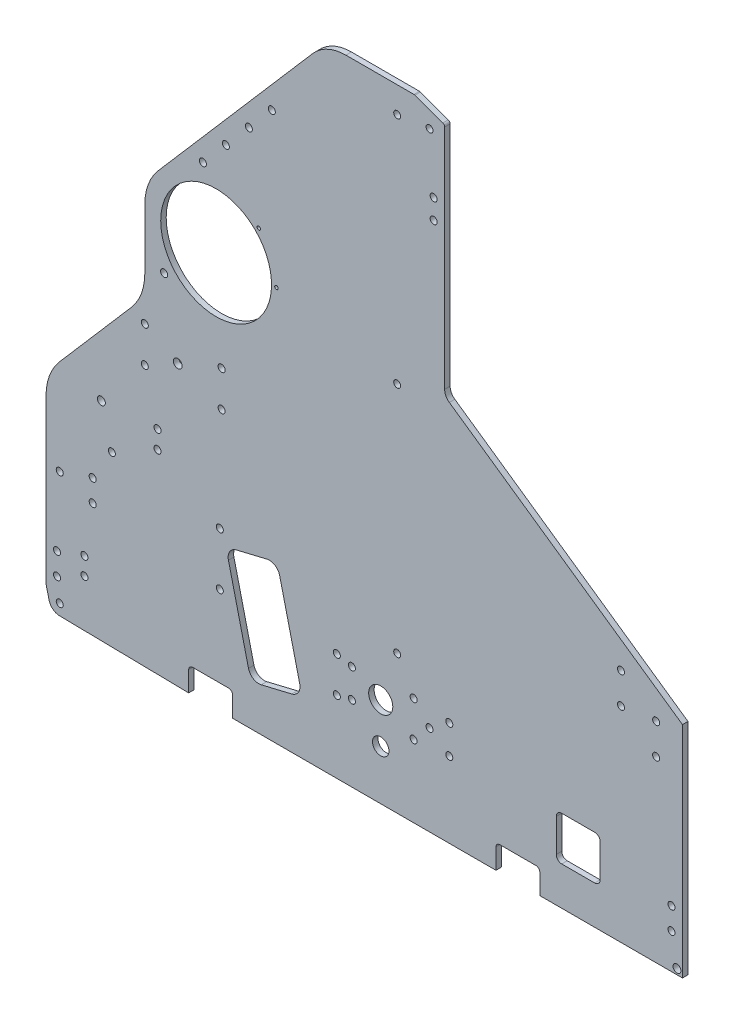
SolidWorks part; units mm, degrees
ref_plane "Front Plane" through (0, 0, 0) normal (0, 0, 1) x (1, 0, 0)
ref_plane "Top Plane" through (0, 0, 0) normal (0, 1, 0) x (1, 0, 0)
ref_plane "Right Plane" through (0, 0, 0) normal (1, 0, 0) x (0, 0, -1)
sketch "Sketch1" plane through (0, 0, 0) normal (0, 0, 1) x (1, 0, 0)
  line L0 (82.55, -20.32) -> (82.55, -6.35)
  line L2 (0, 0) -> (0, 157.48)
  line L4 (368.3, -20.32) -> (368.3, 106.68)
  line L5 (82.55, -6.35) -> (107.95, -6.35)
  line L6 (107.95, -6.35) -> (107.95, -20.32)
  line L7 (107.95, -20.32) -> (260.35, -20.32)
  line L8 (260.35, -20.32) -> (260.35, -6.35)
  line L9 (260.35, -6.35) -> (285.75, -6.35)
  line L10 (285.75, -6.35) -> (285.75, -20.32)
  line L11 (285.75, -20.32) -> (368.3, -20.32)
  line L12 (361.95, 12.7) -> (368.3, 12.7) construction
  line L13 (0, 0) -> (6.35, 0) construction
  line L14 (0.1896, -7.8901) -> (1.7771, -14.2401)
  line L15 (7.8295, -19.0491) -> (82.55, -20.32)
  line L16 (0, 0) -> (0, -6.35)
  line L17 (76.2, 141.605) -> (79.375, 141.605) construction
  line L18 (57.15, 131.2863) -> (101.6, 131.2862) construction
  line L19 (57.15, 131.2863) -> (57.15, 151.9238) construction
  line L20 (101.6, 131.2862) -> (101.6, 151.9237) construction
  line L21 (57.15, 151.9238) -> (101.6, 151.9237) construction
  line L22 (57.15, 131.2863) -> (101.6, 151.9237) construction
  line L23 (101.6, 131.2862) -> (57.15, 151.9238) construction
  line L25 (203.2, 59.805) -> (203.2, 194.805) construction
  line L26 (203.2, 194.805) -> (203.2, 329.805) construction
  line L27 (355.6, 332.105) -> (330.2, 332.105) construction
  line L28 (330.2, 332.105) -> (330.2, 217.805) construction
  line L29 (330.2, 217.805) -> (355.6, 217.805) construction
  line L30 (355.6, 217.805) -> (355.6, 332.105) construction
  line L31 (203.2, 344.805) -> (203.2, 194.805) construction
  line L32 (50.8, 332.105) -> (76.2, 332.105) construction
  line L33 (76.2, 332.105) -> (76.2, 217.805) construction
  line L34 (50.8, 217.805) -> (50.8, 332.105) construction
  line L35 (76.2, 217.805) -> (50.8, 217.805) construction
  line L36 (213.2, 344.805) -> (230.6638, 338.455)
  line L37 (203.2, 344.805) -> (161.925, 344.805)
  line L38 (203.2, 344.805) -> (213.2, 344.805)
  line L39 (348.5362, 344.805) -> (413.4623, 344.805)
  line L40 (348.5362, 344.805) -> (230.6638, 344.805) construction
  line L42 (161.925, 344.805) -> (0, 157.48)
  line L44 (230.6638, 338.455) -> (230.6638, 202.565)
  line L45 (230.6638, 202.565) -> (368.3, 106.68)
  line L46 (213.2, 344.805) -> (-141.0713, 344.805) construction
  circle A0 centre (6.35, 0) radius 2.032
  circle A1 centre (6.35, 12.7) radius 2.032
  circle A2 centre (361.95, 0) radius 2.032
  circle A3 centre (361.95, 12.7) radius 2.032
  arc A5 (1.7771, -14.2401) -> (7.8295, -19.0491) centre (7.9375, -12.7) ccw
  circle A6 centre (7.9375, -12.7) radius 2.032
  arc A7 (0, -6.35) -> (0.1896, -7.8901) centre (6.35, -6.35) ccw
  circle A8 centre (38.1, 78.105) radius 2.032
  circle A9 centre (76.2, 141.605) radius 2.54
  circle A10 centre (101.6, 131.2862) radius 2.032
  circle A11 centre (101.6, 151.9237) radius 2.032
  circle A12 centre (57.15, 151.9238) radius 2.032
  circle A13 centre (57.15, 131.2863) radius 2.032
  circle A15 centre (203.2, 59.805) radius 2
  circle A16 centre (203.2, 194.805) radius 2
  circle A17 centre (203.2, 329.805) radius 2
  circle A18 centre (63.5, 313.055) radius 2.032
  circle A20 centre (355.6, 332.105) radius 2.032
  circle A21 centre (330.2, 332.105) radius 2.032
  circle A22 centre (355.6, 217.805) radius 2.032
  circle A23 centre (330.2, 217.805) radius 2.032
  circle A24 centre (50.8, 332.105) radius 2.032
  circle A25 centre (76.2, 332.105) radius 2.032
  circle A26 centre (50.8, 217.805) radius 2.032
  circle A27 centre (76.2, 217.805) radius 2.032
  circle A28 centre (221.9319, 332.105) radius 2
  circle A29 centre (224.3138, 298.831) radius 2.032
  circle A30 centre (353.06, 100.7351) radius 2.032
  circle A31 centre (332.74, 115.9751) radius 2.032
  circle A32 centre (332.74, 98.1951) radius 2.032
  circle A33 centre (353.06, 82.9551) radius 2.032
  circle A34 centre (117.3562, 280.4276) radius 2.032
  circle A35 centre (104.0678, 265.0548) radius 2.032
  circle A36 centre (90.7795, 249.682) radius 2.032
  circle A38 centre (130.6445, 295.8004) radius 2.032
  circle A39 centre (68.326, 182.9237) radius 2.032
  circle A40 centre (224.3138, 287.401) radius 2.032
  point P82 (203.2, 344.805)
  point P83 (221.9319, 341.63)
  point P90 (368.3, 62.484)
  dimension "D6" = 4.064
  dimension "D10" = 6.35
  dimension "D11" = 4.064
  dimension "D17" = 38.1
  dimension "D27" = 4
  dimension "D31" = 4.064
  dimension "D32" = 41.275
  dimension "D36" = 4.064
  dimension "D47" = 39.624
  dimension "D48" = 4.064
  dimension "D25" = 5.08
  dimension "D26" = 4.064
  dimension "D52" = 4.064
  dimension "D65" = 4.064
  dimension "D2" = 127
  dimension "D3" = 13.97
  dimension "D4" = 25.4
  dimension "D5" = 152.4
  dimension "D7" = 12.7
  dimension "D8" = 6.35
  dimension "D9" = 20.32
  dimension "D12" = 12.7
  dimension "D13" = 1.5875
  dimension "D14" = 82.55
  dimension "D15" = 368.3
  dimension "D16" = 6.35
  dimension "D18" = 98.425
  dimension "D19" = 38.1
  dimension "D20" = 63.5
  dimension "D21" = 3.175
  dimension "D22" = 270
  dimension "D23" = 20.6375
  dimension "D24" = 44.45
  dimension "D28" = 135
  dimension "D29" = 12.7
  dimension "D30" = 15
  dimension "D33" = 63.5
  dimension "D34" = 27.4638
  dimension "D35" = 12.7
  dimension "D37" = 114.3
  dimension "D38" = 25.4
  dimension "D39" = 12.7
  dimension "D40" = 157.48
  dimension "D41" = 142.24
  dimension "D42" = 365.125
  dimension "D43" = 10
  dimension "D44" = 6.35
  dimension "D45" = 31.75
  dimension "D46" = 6.35
  dimension "D49" = 6.35
  dimension "D50" = 203.2
  dimension "D51" = 15.24
  dimension "D53" = 17.78
  dimension "D54" = 17.78
  dimension "D55" = 20.32
  dimension "D56" = 15.24
  dimension "D57" = 92.202
  dimension "D58" = 8.382
  dimension "D59" = 20.32
  dimension "D60" = 20.32
  dimension "D61" = 8.382
  dimension "D62" = 20.32
  dimension "D63" = 8.382
  dimension "D64" = 8.382
  dimension "D66" = 35.052
  dimension "D67" = 68.326
  dimension "D68" = 11.43
extrude "Boss-Extrude1" add sketch "Sketch1" along normal blind 3.175 contours L16 A7 L14 A5 L15 L2 A0 A1 A6 region at (171.3489, 119.5243, 0)
fillet "Fillet1" radius 2.286 4 edges at (285.75, -6.35, 1.5875) (107.95, -6.35, 1.5875) (260.35, -6.35, 1.5875) (82.55, -6.35, 1.5875)
fillet "Fillet2" radius 6.35 1 edges at (230.6638, 202.565, 1.5875)
sketch "Sketch2" plane through (0, 0, 0) normal (0, 0, -1) x (-1, 0, 0)
  circle A0 centre (-100.5528, 71.086) radius 2.032 construction
  circle A1 centre (-100.5528, 40.606) radius 2.032 construction
  circle A2 centre (-22.225, 18.2025) radius 2.032 construction
  circle A3 centre (-22.225, 8.0425) radius 2.032 construction
  circle A4 centre (-100.5528, 71.086) radius 2.032
  circle A5 centre (-100.5528, 40.606) radius 2.032
  circle A6 centre (-22.225, 18.2025) radius 2.032
  circle A7 centre (-22.225, 8.0425) radius 2.032
extrude "Cut-Extrude1" cut sketch "Sketch2" against normal through all
fillet "Fillet3" radius 1.5875 2 edges at (230.6638, 338.455, 1.5875) (213.2, 344.805, 1.5875)
sketch "Sketch3" plane through (0, 0, 3.175) normal (0, 0, 1) x (1, 0, 0)
  line L0 (132.9524, 63.2646) -> (132.7215, 64.2281) construction
  line L1 (128.3815, 66.8898) -> (110.6829, 62.6472) construction
  line L2 (114.5132, 58.4237) -> (126.8822, 61.3887) construction
  line L3 (108.0212, 58.3072) -> (108.2522, 57.3436) construction
  line L4 (131.2006, 57.703) -> (140.0164, 20.9266) construction
  line L5 (144.0993, 16.7636) -> (132.9524, 63.2646) construction
  line L6 (108.2522, 57.3436) -> (119.3991, 10.8427) construction
  line L7 (121.1509, 16.4042) -> (112.3351, 53.1807) construction
  line L8 (119.3991, 10.8427) -> (119.6301, 9.8791) construction
  line L9 (144.3303, 15.8001) -> (144.0993, 16.7636) construction
  line L10 (137.8383, 15.6835) -> (125.4694, 12.7185) construction
  line L11 (123.9701, 7.2175) -> (141.6687, 11.4601) construction
  line L12 (132.9524, 63.2646) -> (132.7215, 64.2281)
  line L13 (128.3815, 66.8898) -> (110.6829, 62.6472)
  line L14 (114.5132, 58.4237) -> (126.8822, 61.3887)
  line L15 (108.0212, 58.3072) -> (108.2522, 57.3436)
  line L16 (131.2006, 57.703) -> (140.0164, 20.9266)
  line L17 (144.0993, 16.7636) -> (132.9524, 63.2646)
  line L18 (108.2522, 57.3436) -> (119.3991, 10.8427)
  line L19 (121.1509, 16.4042) -> (112.3351, 53.1807)
  line L20 (119.3991, 10.8427) -> (119.6301, 9.8791)
  line L21 (144.3303, 15.8001) -> (144.0993, 16.7636)
  line L22 (137.8383, 15.6835) -> (125.4694, 12.7185)
  line L23 (123.9701, 7.2175) -> (141.6687, 11.4601)
  line L24 (127.7894, 69.3598) -> (110.0908, 65.1172)
  line L25 (105.5512, 57.7151) -> (105.7822, 56.7515)
  line L26 (105.7822, 56.7515) -> (116.9291, 10.2506)
  line L27 (116.9291, 10.2506) -> (117.16, 9.287)
  line L28 (124.5622, 4.7475) -> (142.2608, 8.9901)
  line L29 (146.8003, 16.3922) -> (146.5694, 17.3557)
  line L30 (146.5694, 17.3557) -> (135.4225, 63.8567)
  line L31 (135.4225, 63.8567) -> (135.1915, 64.8202)
  line L32 (14.605, -0.1369) -> (103.7278, 32.3011) construction
  line L33 (14.605, -0.1369) -> (103.7278, 32.3011)
  line L35 (-39.6666, 74.7152) -> (103.7278, 126.9065) construction
  arc A0 (132.7215, 64.2281) -> (128.6308, 66.9403) centre (129.2206, 63.3889) ccw construction
  arc A1 (110.6829, 62.6472) -> (110.4377, 62.5791) centre (111.522, 59.1463) ccw construction
  arc A2 (128.6308, 66.9403) -> (128.3815, 66.8898) centre (129.2206, 63.3889) ccw construction
  arc A3 (110.4377, 62.5791) -> (108.0212, 58.3072) centre (111.522, 59.1463) ccw construction
  arc A4 (119.6301, 9.8791) -> (123.7207, 7.167) centre (123.1309, 10.7183) ccw construction
  arc A5 (141.9139, 11.5281) -> (144.3303, 15.8001) centre (140.8295, 14.9609) ccw construction
  arc A6 (141.6687, 11.4601) -> (141.9139, 11.5281) centre (140.8295, 14.9609) ccw construction
  arc A7 (123.7207, 7.167) -> (123.9701, 7.2175) centre (123.1309, 10.7183) ccw construction
  arc A8 (132.7215, 64.2281) -> (128.6308, 66.9403) centre (129.2206, 63.3889) ccw
  arc A9 (110.6829, 62.6472) -> (110.4377, 62.5791) centre (111.522, 59.1463) ccw
  arc A10 (128.6308, 66.9403) -> (128.3815, 66.8898) centre (129.2206, 63.3889) ccw
  arc A11 (110.4377, 62.5791) -> (108.0212, 58.3072) centre (111.522, 59.1463) ccw
  arc A12 (119.6301, 9.8791) -> (123.7207, 7.167) centre (123.1309, 10.7183) ccw
  arc A13 (141.9139, 11.5281) -> (144.3303, 15.8001) centre (140.8295, 14.9609) ccw
  arc A14 (141.6687, 11.4601) -> (141.9139, 11.5281) centre (140.8295, 14.9609) ccw
  arc A15 (123.7207, 7.167) -> (123.9701, 7.2175) centre (123.1309, 10.7183) ccw
  arc A16 (110.0908, 65.1172) -> (109.6726, 65.0012) centre (111.522, 59.1463) ccw
  arc A17 (109.6726, 65.0012) -> (105.5512, 57.7151) centre (111.522, 59.1463) ccw
  arc A18 (117.16, 9.287) -> (124.1369, 4.6613) centre (123.1309, 10.7183) ccw
  arc A19 (124.1369, 4.6613) -> (124.5622, 4.7475) centre (123.1309, 10.7183) ccw
  arc A20 (142.2608, 8.9901) -> (142.679, 9.1061) centre (140.8295, 14.9609) ccw
  arc A21 (142.679, 9.1061) -> (146.8003, 16.3922) centre (140.8295, 14.9609) ccw
  arc A22 (135.1915, 64.8202) -> (128.2147, 69.446) centre (129.2206, 63.3889) ccw
  arc A23 (128.2147, 69.446) -> (127.7894, 69.3598) centre (129.2206, 63.3889) ccw
  circle A24 centre (64.5259, 102.9405) radius 2.032 construction
  circle A25 centre (64.5259, 92.5258) radius 2.032 construction
  circle A26 centre (133.35, 208.2281) radius 1.016 construction
  circle A33 centre (26.9875, 46.9531) radius 2.032
  circle A34 centre (26.9875, 59.6531) radius 2.032
  circle A35 centre (7.9375, 53.3031) radius 2.032
  circle A36 centre (7.9375, 53.3031) radius 2.032 construction
  circle A37 centre (32.0306, 100.8109) radius 31.75 construction
  circle A38 centre (32.0306, 100.8109) radius 2.286
  circle A39 centre (123.1207, 232.9238) radius 1.016 construction
  circle A40 centre (64.5259, 102.9405) radius 2.032
  circle A41 centre (64.5259, 92.5258) radius 2.032
  circle A42 centre (133.35, 208.2281) radius 1.016
  circle A43 centre (123.1207, 232.9238) radius 1.016
  circle A44 centre (26.9875, 59.6531) radius 2.032 construction
  circle A45 centre (26.9875, 46.9531) radius 2.032 construction
  ellipse E0 centre (124.5975, 48.8487) end of major axis (128.5376, 61.3578) minor radius 6 (131.2006, 57.703) -> (126.8822, 61.3887) ccw construction
  ellipse E1 centre (122.2349, 48.2824) end of major axis (113.0518, 57.6456) minor radius 6 (114.5132, 58.4237) -> (112.3351, 53.1807) ccw construction
  ellipse E2 centre (127.7541, 25.2585) end of major axis (131.6942, 37.7675) minor radius 6 (121.1509, 16.4042) -> (125.4694, 12.7185) ccw construction
  ellipse E3 centre (130.1166, 25.8248) end of major axis (139.2998, 16.4616) minor radius 6 (137.8383, 15.6835) -> (140.0164, 20.9266) ccw construction
  ellipse E4 centre (124.5975, 48.8487) end of major axis (120.6573, 36.3397) minor radius 6 (131.2006, 57.703) -> (126.8822, 61.3887) ccw
  ellipse E5 centre (122.2349, 48.2824) end of major axis (131.4181, 38.9192) minor radius 6 (114.5132, 58.4237) -> (112.3351, 53.1807) ccw
  ellipse E6 centre (127.7541, 25.2585) end of major axis (131.6942, 37.7675) minor radius 6 (121.1509, 16.4042) -> (125.4694, 12.7185) ccw
  ellipse E7 centre (130.1166, 25.8248) end of major axis (139.2998, 16.4616) minor radius 6 (137.8383, 15.6835) -> (140.0164, 20.9266) ccw
  point P115 (32.0306, 100.8109)
  dimension "D3" = 63.5
  dimension "D4" = 4.572
  dimension "D2" = 88.9
  dimension "D1" = 2.54
extrude "Cut-Extrude2" cut sketch "Sketch3" against normal through all contours A22 A23 L24 A16 A17 L25 L26 L27 A18 A19 L28 A20 A21 L29 L30 L31 A15 A12 L20 L18 L15 A11 A9 L13 A10 A8 L12 L17 L21 A13 A14 L23 | A12 A15 L23 A14 A13 L21 L17 L12 A8 A10 L13 A9 A11 L15 L18 L20 E7 L22 E6 L19 E5 L14 E4 L16 | L22 E7 L16 E4 L14 E5 L19 E6 | A38 | A41 | A40 | A35 | A34 | A33 | A43 | A42 region at (137.844, 39.8506, 3.175) region at (126.1758, 37.0536, 3.175) region at (128.1544, 68.6508, 3.175) region at (32.0306, 100.8109, 3.175) region at (64.5259, 102.9405, 3.175) region at (64.5259, 92.5258, 3.175)
sketch "Sketch4" plane through (0, 0, 3.175) normal (0, 0, 1) x (1, 0, 0)
  line L0 (57.15, 151.9238) -> (101.6, 151.9237) construction
  line L1 (168.275, 21.4312) -> (212.725, 21.4312) construction
  line L2 (168.275, 21.4312) -> (168.275, 42.0687) construction
  line L3 (168.275, 42.0687) -> (212.725, 42.0687) construction
  line L4 (212.725, 21.4312) -> (212.725, 42.0687) construction
  line L5 (168.275, 21.4312) -> (212.725, 42.0687) construction
  line L6 (168.275, 42.0687) -> (212.725, 21.4312) construction
  line L7 (57.15, 131.2863) -> (57.15, 151.9238) construction
  line L8 (107.95, -20.32) -> (260.35, -20.32) construction
  line L9 (193.675, 31.75) -> (177.005, 31.75) construction
  line L10 (190.5, 31.75) -> (193.675, 31.75) construction
  line L11 (6.35, 12.7) -> (361.95, 12.7) construction
  line L12 (107.95, -6.35) -> (107.95, -20.32) construction
  line L13 (193.675, 31.75) -> (220.6625, 31.75) construction
  line L14 (177.005, 23.4569) -> (177.005, 40.0431) construction
  line L15 (213.2, 44.805) -> (193.2, 44.805) construction
  line L16 (213.2, 44.805) -> (213.2, 344.805) construction
  line L17 (213.2, 344.805) -> (193.2, 344.805) construction
  line L18 (193.2, 44.805) -> (193.2, 344.805) construction
  line L19 (213.2, 44.805) -> (193.2, 344.805) construction
  line L20 (213.2, 344.805) -> (193.2, 44.805) construction
  line L21 (226.9319, 332.105) -> (226.9319, 31.75) construction
  line L22 (237.33, 40.0431) -> (233.3612, 40.0431) construction
  line L23 (237.33, 23.4569) -> (233.3612, 23.4569) construction
  circle A0 centre (168.275, 42.0687) radius 2.032
  circle A1 centre (212.725, 42.0687) radius 2.032
  circle A2 centre (212.725, 21.4312) radius 2.032
  circle A3 centre (168.275, 21.4312) radius 2.032
  circle A4 centre (193.675, 31.75) radius 6.985
  circle A7 centre (220.6625, 31.75) radius 14.2875 construction
  circle A8 centre (193.675, 31.75) radius 12.7 construction
  circle A9 centre (177.005, 40.0431) radius 2.032
  circle A10 centre (177.005, 23.4569) radius 2.032
  circle A11 centre (237.33, 40.0431) radius 2.032 construction
  circle A12 centre (237.33, 23.4569) radius 2.032 construction
  circle A13 centre (193.675, 8.4667) radius 4.7625
  circle A14 centre (221.9319, 31.75) radius 2.032
  circle A15 centre (221.9319, 31.75) radius 5 construction
  circle A16 centre (221.9319, 332.105) radius 5 construction
  circle A17 centre (233.3612, 23.4569) radius 2.032
  circle A18 centre (233.3612, 40.0431) radius 2.032
  point P0 (190.5, 31.75)
  point P26 (203.2, 194.805)
  point P38 (177.005, 31.75)
  dimension "D1" = 4.064
  dimension "D4" = 13.97
  dimension "D7" = 9.525
  dimension "D10" = 25.4
  dimension "D11" = 28.575
  dimension "D16" = 10
  dimension "D17" = 4.064
  dimension "D18" = 10
  dimension "D2" = 52.07
  dimension "D3" = 3.175
  dimension "D5" = 82.55
  dimension "D6" = 26.9875
  dimension "D8" = 20
  dimension "D9" = 300
  dimension "D12" = 16.67
  dimension "D13" = 16.5862
  dimension "D14" = 60.325
  dimension "D15" = 23.2833
  dimension "D19" = 3.9688
extrude "Cut-Extrude3" cut sketch "Sketch4" against normal through all
sketch "Sketch5" plane through (0, 0, -187.325) normal (0, 0, -1) x (-1, 0, 0)
  line L0 (-57.15, 223.5947) -> (-57.15, 165.3337)
  line L1 (-161.925, 344.805) -> (-52.7201, 218.4699) construction
  line L2 (-57.15, 165.3337) -> (0, 99.219)
  line L3 (0, -6.35) -> (0, 157.48) construction
  line L4 (-50.4199, 215.8089) -> (0, 157.48) construction
  line L5 (-50.4199, 215.8089) -> (0, 157.48) construction
  line L6 (-57.15, 223.5947) -> (0, 157.48)
  line L7 (0, 157.48) -> (0, 99.219)
  circle A0 centre (-98.425, 208.2281) radius 32.0675
  circle A1 centre (-365.125, -17.145) radius 2.286 construction
  circle A2 centre (-365.125, -17.145) radius 2.286
  dimension "D3" = 64.135
  dimension "D1" = 38.1
  dimension "D2" = 57.15
  dimension "D4" = 41.275
  dimension "D5" = 41.275
extrude "Cut-Extrude5" cut sketch "Sketch5" against normal through all contours A0 | L7 L6 L0 L2 | A2 region at (28.575, 161.4068, -187.325) region at (98.425, 208.2281, -187.325)
fillet "Fillet4" radius 31.75 3 edges at (0, 99.219, 1.5875) (57.15, 165.3337, 1.5875) (57.15, 223.5947, 1.5875)
sketch "Sketch6" plane through (0, 0, 3.175) normal (0, 0, 1) x (1, 0, 0)
  line L0 (285.75, -20.32) -> (368.3, -20.32) construction
  line L1 (298.45, 27.305) -> (317.5, 27.305)
  line L2 (295.275, 24.13) -> (295.275, 5.08)
  line L3 (298.45, 1.905) -> (317.5, 1.905)
  line L4 (320.675, 24.13) -> (320.675, 5.08)
  line L5 (295.275, 27.305) -> (320.675, 1.905) construction
  line L6 (295.275, 1.905) -> (320.675, 27.305) construction
  line L7 (368.3, -20.32) -> (368.3, 106.68) construction
  arc A0 (295.275, 5.08) -> (298.45, 1.905) centre (298.45, 5.08) ccw
  arc A1 (317.5, 1.905) -> (320.675, 5.08) centre (317.5, 5.08) ccw
  arc A2 (317.5, 27.305) -> (320.675, 24.13) centre (317.5, 24.13) cw
  arc A3 (298.45, 27.305) -> (295.275, 24.13) centre (298.45, 24.13) ccw
  point P0 (307.975, 14.605)
  dimension "D2" = 3.175
  dimension "D1" = 25.4
  dimension "D3" = 22.225
  dimension "D4" = 47.625
extrude "Cut-Extrude6" cut sketch "Sketch6" against normal through all
sketch "Sketch7" plane through (0, 0, 0) normal (0, 0, -1) x (-1, 0, 0)
  circle A0 centre (-215.9, 306.705) radius 2.032 construction
  arc A1 (-201.2648, 307.3246) -> (-201.2648, 306.0854) centre (-203.2, 306.705) ccw construction
  arc A2 (-192.4352, 306.0854) -> (-192.4352, 307.3246) centre (-190.5, 306.705) ccw construction
  arc A3 (-176.9699, 308.5597) -> (-176.9699, 304.8503) centre (-177.8, 306.705) ccw construction
  circle A4 centre (-215.9, 255.905) radius 2.032 construction
  arc A5 (-201.2648, 256.5246) -> (-201.2648, 255.2854) centre (-203.2, 255.905) ccw construction
  arc A6 (-192.4352, 255.2854) -> (-192.4352, 256.5246) centre (-190.5, 255.905) ccw construction
  arc A7 (-176.9699, 257.7597) -> (-176.9699, 254.0503) centre (-177.8, 255.905) ccw construction
  circle A8 centre (-215.9, 306.705) radius 2.032
  arc A9 (-201.2648, 307.3246) -> (-201.2648, 306.0854) centre (-203.2, 306.705) ccw
  arc A10 (-192.4352, 306.0854) -> (-192.4352, 307.3246) centre (-190.5, 306.705) ccw
  arc A11 (-176.9699, 308.5597) -> (-176.9699, 304.8503) centre (-177.8, 306.705) ccw
  circle A12 centre (-215.9, 255.905) radius 2.032
  arc A13 (-201.2648, 256.5246) -> (-201.2648, 255.2854) centre (-203.2, 255.905) ccw
  arc A14 (-192.4352, 255.2854) -> (-192.4352, 256.5246) centre (-190.5, 255.905) ccw
  arc A15 (-176.9699, 257.7597) -> (-176.9699, 254.0503) centre (-177.8, 255.905) ccw
  circle A16 centre (-203.2, 306.705) radius 2.032
  circle A17 centre (-190.5, 306.705) radius 2.032
  circle A18 centre (-177.8, 306.705) radius 2.032
  circle A19 centre (-177.8, 255.905) radius 2.032
  circle A20 centre (-190.5, 255.905) radius 2.032
  circle A21 centre (-203.2, 255.905) radius 2.032
  dimension "D1" = 4.064
extrude "Cut-Extrude7" cut sketch "Sketch7" against normal blind 2.54 contours A12 | A13 A21 | A14 A20 | A15 A19 | A8 | A9 A16 | A10 A17 | A11 A18 region at (215.9, 306.705, 0) region at (203.2, 306.705, 0) region at (190.5, 306.705, 0) region at (177.8, 306.705, 0) region at (215.9, 255.905, 0) region at (203.2, 255.905, 0) region at (190.5, 255.905, 0) region at (177.8, 255.905, 0)
fillet "Fillet5" radius 25.4 1 edges at (161.925, 344.805, 1.5875)
